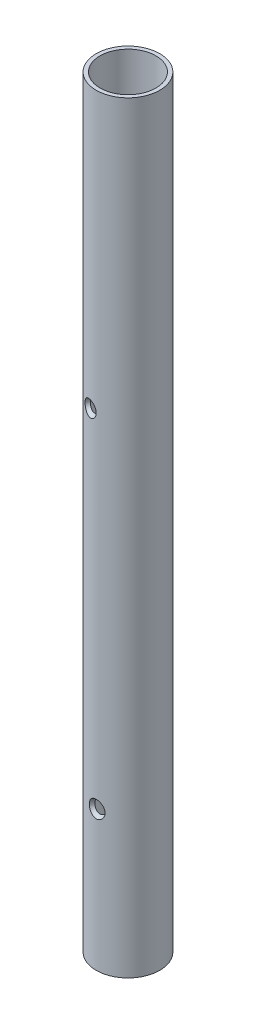
SolidWorks part; units mm, degrees
material "6063-T1"
ref_plane "Front Plane" through (0, 0, 0) normal (0, 0, 1) x (1, 0, 0)
ref_plane "Top Plane" through (0, 0, 0) normal (0, 1, 0) x (1, 0, 0)
ref_plane "Right Plane" through (0, 0, 0) normal (1, 0, 0) x (0, 0, -1)
sketch "Sketch1" plane through (0, 0, 0) normal (0, 1, 0) x (1, 0, 0)
  circle A0 centre (0, 0) radius 22
  circle A1 centre (0, 0) radius 25
  dimension "D1" = 50
  dimension "D2" = 3
extrude "Boss-Extrude1" add sketch "Sketch1" along normal blind 600
revolve "Cut-Revolve3" cut sketch "Sketch4" angle 360 about L0
sketch "Sketch4" plane through (-103.1364, 380, -329.9949) normal (0, -1, 0) x (-1, 0, 0)
  line L0 (-96.4969, -304.9949) -> (-96.4969, -316.4949)
  line L1 (-96.4969, -316.4949) -> (-103.1364, -304.9949)
  line L3 (-103.1364, -304.9949) -> (-96.4969, -304.9949)
revolve "Cut-Revolve4" cut sketch "Sketch5" angle 360 about L0
sketch "Sketch5" plane through (-103.1364, 110, -329.9949) normal (0, -1, 0) x (-1, 0, 0)
  line L0 (-103.1364, -304.9949) -> (-103.1364, -316.4949)
  line L2 (-103.1364, -316.4949) -> (-96.4969, -304.9949)
  line L3 (-96.4969, -304.9949) -> (-103.1364, -304.9949)
mirror "Mirror3" about plane through (0, 0, 0) normal (0, 0, 1) of "Cut-Revolve4", "Cut-Revolve3"
